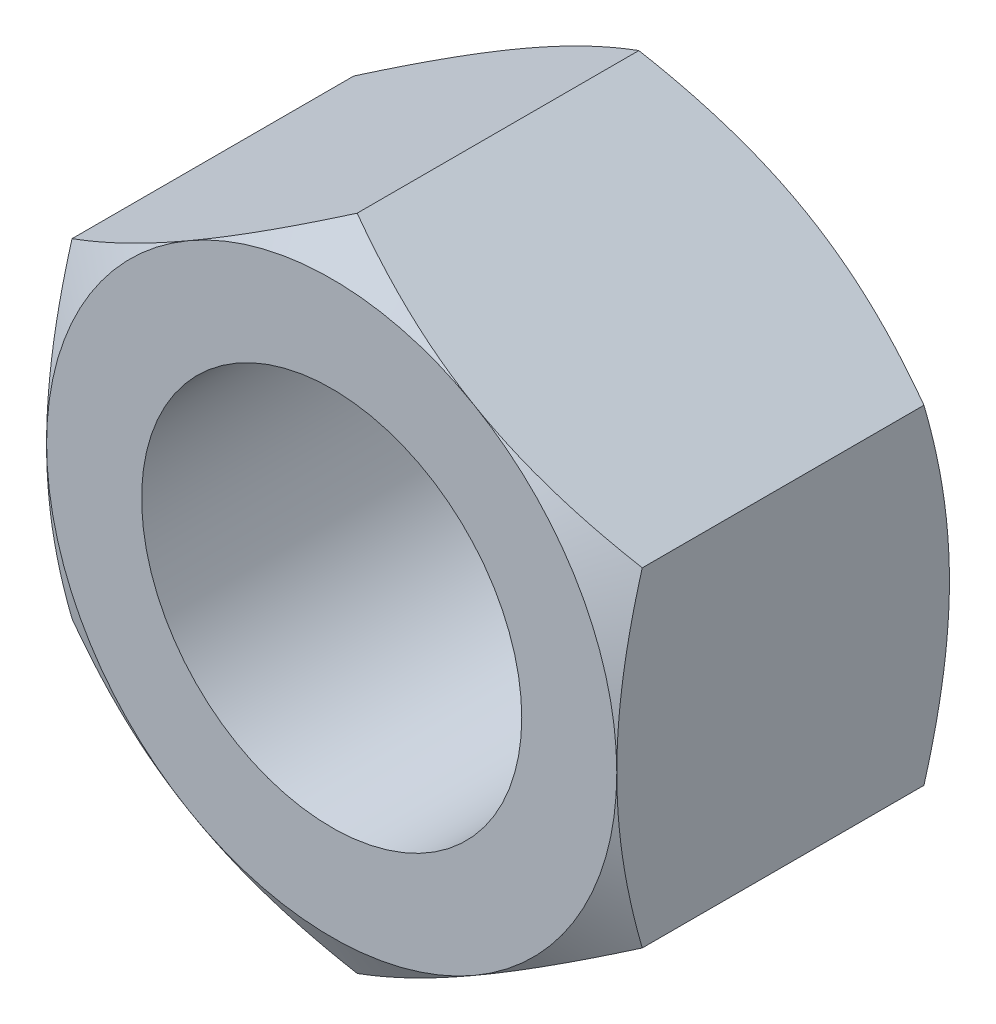
SolidWorks part; units mm, degrees
ref_plane "Front" through (0, 0, 0) normal (0, 0, 1) x (1, 0, 0)
ref_plane "Top" through (0, 0, 0) normal (0, 1, 0) x (1, 0, 0)
ref_plane "Right" through (0, 0, 0) normal (1, 0, 0) x (0, 0, -1)
sketch "Sketch1" plane through (0, 0, 0) normal (0, 0, 1) x (1, 0, 0)
  line L1 (-7.1438, 4.1244) -> (-7.1437, -4.1244)
  line L2 (-7.1437, -4.1244) -> (0, -8.2489)
  line L3 (0, -8.2489) -> (7.1438, -4.1244)
  line L4 (7.1438, -4.1244) -> (7.1438, 4.1244)
  line L5 (7.1438, 4.1244) -> (0, 8.2489)
  line L6 (0, 8.2489) -> (-7.1438, 4.1244)
  circle A0 centre (0, 0) radius 7.1438 construction
  circle A1 centre (0, 0) radius 4.7625
  point P10 (0, 4.7625)
  dimension "hex" = 14.2875
  dimension "dia" = 9.525
extrude "Extrude1" add sketch "Sketch1" along normal mid plane 8.3344
sketch "Sketch4" plane through (0, 0, -4.1672) normal (0, 0, -1) x (-1, 0, 0)
  circle A0 centre (0, 0) radius 4.7625 construction
  circle A1 centre (0, 0) radius 4.7625
curve "Helix/Spiral3" [suppressed] pitch 1.5875 height 10.0012 turns 6.3
sketch "Sketch3" plane through (0, 0, 0) normal (1, 0, 0) x (0, 0, -1)
  line L0 (4.1672, 4.7625) -> (5.5562, 4.7625)
  line L1 (5.5562, 4.7625) -> (4.9609, 3.7314)
  line L2 (4.9609, 3.7314) -> (4.7625, 3.7314)
  line L3 (4.7625, 3.7314) -> (4.1672, 4.7625)
  line L4 (4.4648, 4.2469) -> (5.2586, 4.2469) construction
  dimension "D1" = 60
  dimension "D2" = 0.7937
  dimension "D3" = 0.1984
sweep "Sweep1" [suppressed] add profiles "Sketch3" path "Helix/Spiral3"
sketch "Sketch6" [suppressed] plane through (0, 0, 0) normal (1, 0, 0) x (0, 0, -1)
  line L0 (-4.5641, 5.1594) -> (-3.7703, 4.3656)
  line L1 (-3.7703, 4.3656) -> (-3.7703, 0) construction
  line L2 (3.9291, 0) -> (-3.9291, 0) construction
  line L3 (-3.7703, 0) -> (-5.8336, 0)
  line L4 (-5.8336, 0) -> (-5.8336, 5.1594)
  line L5 (-5.8336, 5.1594) -> (-4.5641, 5.1594)
  line L6 (-3.7703, 4.3656) -> (0.5953, 0)
  line L7 (0.5953, 0) -> (-3.7703, 0)
  line L8 (-4.1672, -4.1244) -> (-4.1672, 4.1244) construction
  point P2 (-4.1672, 4.7625)
  dimension "D2" = 0.7937
  dimension "D1" = 45
revolve "Cut-Revolve1" [suppressed] cut sketch "Sketch6" angle 360 about L3
sketch "Sketch7" plane through (0, 0, 4.1672) normal (0, 0, 1) x (1, 0, 0)
  circle A0 centre (0, 0) radius 7.1438 construction
  circle A1 centre (0, 0) radius 7.1438
extrude "Extrude2" cut sketch "Sketch7" against normal blind 25.4 draft 60 flip side to cut
mirror "Mirror1" about plane through (0, 0, 0) normal (0, 0, 1) of "Extrude2", "Cut-Revolve1"
sketch "Sketch8" [suppressed] plane through (0, 0, 4.1672) normal (0, 0, 1) x (1, 0, 0)
  line L0 (-3.3676, 3.3676) -> (0, 0) construction
  line L1 (0, -5.8287) -> (0, 5.8287) construction
  circle A0 centre (0, 0) radius 4.7625 construction
  point P0 (-3.3676, 3.3676)
  dimension "D1" = 45
equation "\"D3@Helix/Spiral3\" = \"length@Extrude1\" * 1.2"
equation "\"D2@Sketch3\" = \"D4@Helix/Spiral3\" * .5"
equation "\"D3@Sketch3\" = \"D4@Helix/Spiral3\" * .125"
equation "\"D2@Sketch6\" = \"D4@Helix/Spiral3\" * .5"
